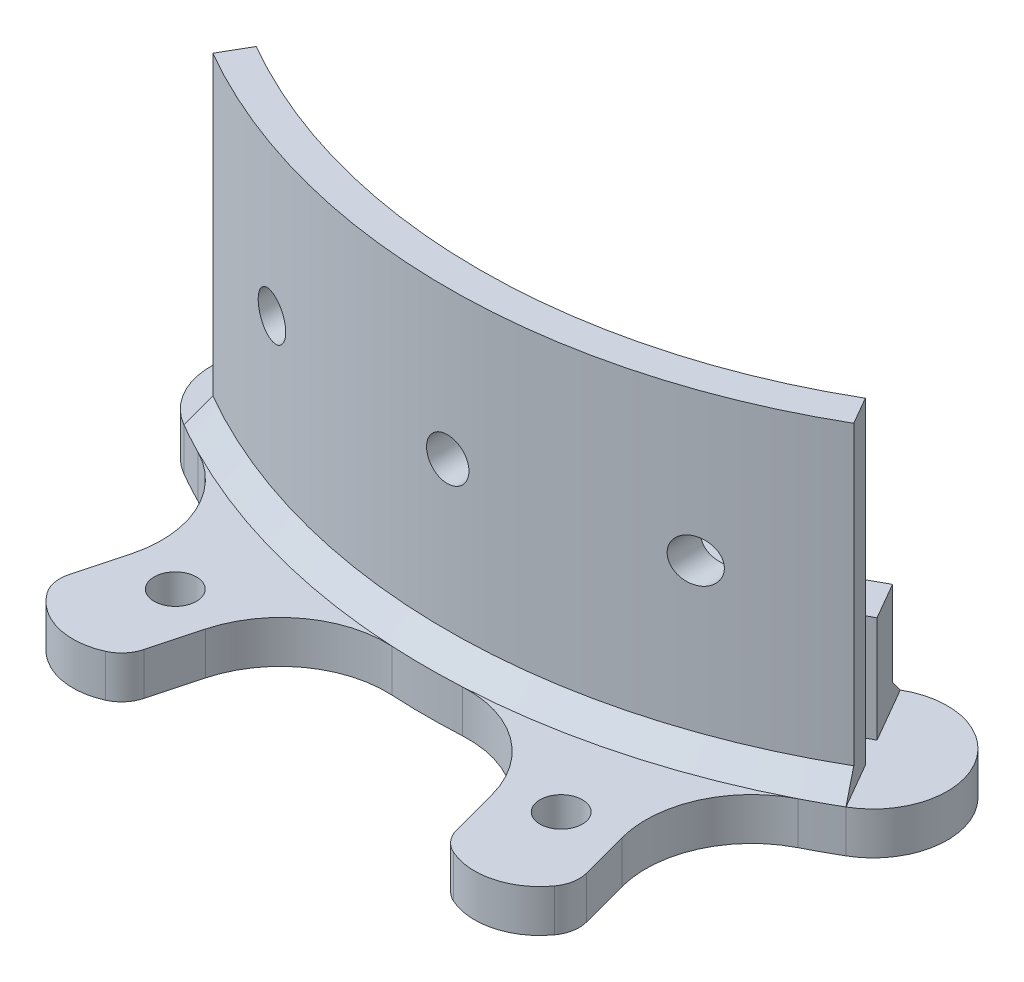
SolidWorks part; units mm, degrees
ref_plane "Front Plane" through (0, 0, 0) normal (0, 0, 1) x (1, 0, 0)
ref_plane "Top Plane" through (0, 0, 0) normal (0, 1, 0) x (1, 0, 0)
ref_plane "Right Plane" through (0, 0, 0) normal (1, 0, 0) x (0, 0, -1)
sketch "Sketch1" plane through (0, 0, 0) normal (0, 1, 0) x (1, 0, 0)
  line L0 (0, 0) -> (0, -54.5) construction
  line L1 (0, 0) -> (0, 55) construction
  line L2 (0, 0) -> (-27.25, -47.1984) construction
  line L3 (0, 0) -> (27.25, -47.1984) construction
  line L4 (-27.25, -47.1984) -> (-25.25, -43.7343)
  line L5 (25.25, -43.7343) -> (27.25, -47.1984)
  arc A0 (-27.25, -47.1984) -> (27.25, -47.1984) centre (0, 0) ccw
  arc A1 (-25.25, -43.7343) -> (25.25, -43.7343) centre (0, 0) ccw
  dimension "D1" = 54.5
  dimension "D2" = 55
  dimension "D3" = 150
  dimension "D4" = 54.5
  dimension "D5" = 4
extrude "Boss-Extrude1" add sketch "Sketch1" along normal blind 10 contours A1 L4 A0 L5
sketch "Sketch3" plane through (0, 0, 0) normal (0, -1, 0) x (1, 0, 0)
  line L0 (0, 0) -> (-27.25, 47.1984) construction
  line L1 (-27.25, 47.1984) -> (27.25, 47.1984) construction
  line L2 (27.25, 47.1984) -> (0, 0) construction
  line L3 (-30.25, 52.3945) -> (-28.75, 49.7965)
  line L4 (28.75, 49.7965) -> (30.25, 52.3945)
  arc A0 (-27.25, 47.1984) -> (27.25, 47.1984) centre (0, 0) cw construction
  arc A1 (-28.75, 49.7965) -> (28.75, 49.7965) centre (0, 0) cw
  arc A2 (-30.25, 52.3945) -> (30.25, 52.3945) centre (0, 0) cw
  dimension "D1" = 3
  dimension "D2" = 3
extrude "Boss-Extrude2" add sketch "Sketch3" against normal blind 30 separate body
sketch "Sketch4" plane through (0, 0, 0) normal (0, -1, 0) x (1, 0, 0)
  line L0 (0, 0) -> (-27.25, 47.1984) construction
  line L1 (-27.25, 47.1984) -> (27.25, 47.1984) construction
  line L2 (27.25, 47.1984) -> (0, 0) construction
  arc A0 (-27.25, 47.1984) -> (27.25, 47.1984) centre (0, 0) cw construction
  arc A1 (-24.25, 42.0022) -> (24.25, 42.0022) centre (0, 0) cw
  arc A2 (-31.25, 54.1266) -> (31.25, 54.1266) centre (0, 0) cw
  arc A3 (-31.25, 54.1266) -> (-24.25, 42.0022) centre (-27.75, 48.0644) ccw
  arc A4 (31.25, 54.1266) -> (24.25, 42.0022) centre (27.75, 48.0644) cw
  dimension "D1" = 6
  dimension "D2" = 8
extrude "Boss-Extrude3" add sketch "Sketch4" along normal blind 4
chamfer "Chamfer1" distance 2 angle 45 2 edges at (0, 0, 60.5) (0, 0, 50.5)
sketch "Sketch5" plane through (0, 0, 0) normal (0, 0, 1) x (1, 0, 0)
  line L0 (-30.25, 16) -> (30.25, 16) construction
  line L1 (-30.25, 30) -> (-30.25, 2) construction
  line L2 (30.25, 30) -> (30.25, 2) construction
  line L3 (0, 16) -> (0, 5.2868) construction
  circle A0 centre (0, 16) radius 2
  circle A1 centre (-20, 16) radius 2
  circle A2 centre (20, 16) radius 2
  dimension "D1" = 4
  dimension "D2" = 4
  dimension "D3" = 20
extrude "Cut-Extrude1" cut sketch "Sketch5" against normal through all both and the other way through all
sketch "Sketch6" plane through (0, -4, 0) normal (0, -1, 0) x (1, 0, 0)
  line L0 (0, 0) -> (31.25, 54.1266) construction
  line L1 (31.25, 54.1266) -> (0, 62.5) construction
  line L2 (0, 62.5) -> (-31.25, 54.1266) construction
  line L3 (-31.25, 54.1266) -> (0, 0) construction
  line L4 (15.625, 58.3133) -> (18.9896, 70.8703) construction
  line L5 (20.954, 58.8828) -> (24.4147, 71.7982)
  line L6 (11.2947, 61.471) -> (14.7554, 74.3864)
  line L7 (20.4546, 57.0192) -> (23.8193, 69.5762) construction
  line L8 (10.7954, 59.6074) -> (14.16, 72.1644) construction
  line L9 (0, 54.5) -> (0, 42.0385) construction
  line L10 (0, 0) -> (0, 54.5) construction
  line L13 (-20.954, 58.8828) -> (-24.4147, 71.7982)
  line L14 (-11.2947, 61.471) -> (-14.7554, 74.3864)
  arc A0 (31.25, 54.1266) -> (-31.25, 54.1266) centre (0, 0) ccw construction
  circle A2 centre (18.2132, 67.9726) radius 2
  arc A3 (20.954, 58.8828) -> (11.2947, 61.471) centre (0, 0) ccw
  arc A4 (1.6355, 64.0592) -> (11.2947, 61.471) centre (-9.6593, 2.5882) cw
  arc A5 (-20.954, 58.8828) -> (-11.2947, 61.471) centre (0, 0) cw
  arc A8 (16.4154, 76.3427) -> (23.9552, 74.3224) centre (18.9541, 70.7378) cw
  arc A9 (24.4147, 71.7982) -> (23.9552, 74.3224) centre (21.5169, 72.5747) ccw
  arc A10 (14.7554, 74.3864) -> (16.4154, 76.3427) centre (17.6532, 73.6099) cw
  circle A11 centre (-18.2132, 67.9726) radius 2
  arc A12 (-20.954, 58.8828) -> (-11.2947, 61.471) centre (0, 0) cw
  arc A13 (-24.4147, 71.7982) -> (-23.9552, 74.3224) centre (-21.5169, 72.5747) cw
  arc A14 (-14.7554, 74.3864) -> (-16.4154, 76.3427) centre (-17.6532, 73.6099) ccw
  arc A15 (-16.4154, 76.3427) -> (-23.9552, 74.3224) centre (-18.9541, 70.7378) ccw
  dimension "D4" = 4
  dimension "D6" = 3
  dimension "D1" = 13
  dimension "D2" = 5
  dimension "D5" = 3
  dimension "D3" = 5
extrude "Boss-Extrude4" add sketch "Sketch6" against normal blind 4
fillet "Fillet1" radius 10 4 edges at (20.954, -2, 58.8828) (11.2947, -2, 61.471) (-20.954, -2, 58.8828) (-11.2947, -2, 61.471)
